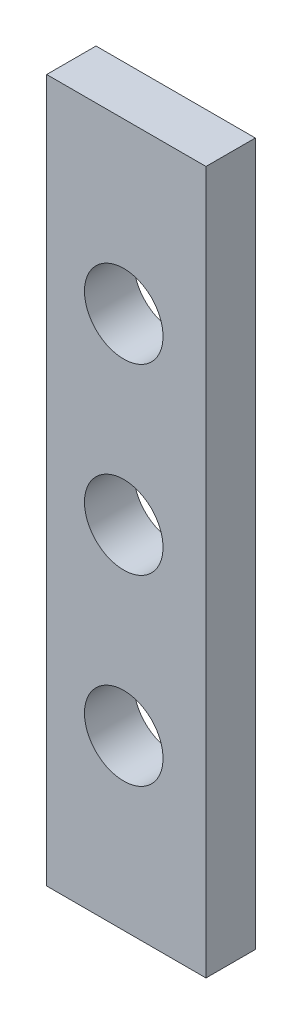
SolidWorks part; units mm, degrees
ref_plane "前视基准面" through (0, 0, 0) normal (0, 0, 1) x (1, 0, 0)
ref_plane "上视基准面" through (0, 0, 0) normal (0, 1, 0) x (1, 0, 0)
ref_plane "右视基准面" through (0, 0, 0) normal (1, 0, 0) x (0, 0, -1)
sketch "草图1" plane through (0, 0, 0) normal (0, 0, 1) x (1, 0, 0)
  line L6 (-130, -105) -> (-121.2816, -105)
  line L7 (-130, -105) -> (-130, -66.5374)
  line L8 (-130, -66.5374) -> (-121.2816, -66.5374)
  line L9 (-121.2816, -105) -> (-121.2816, -66.5374)
  point P1 (-121.2816, -66.5374)
extrude "凸台-拉伸1" add sketch "草图1" along normal blind 2.7
hole_wizard "打孔尺寸(%根据十字)槽沉头木螺钉的类型1" positions "草图2" profile "草图3" countersink size "M4" standard "GB"
sketch "草图2" plane through (40.4914, -131.0101, 7) normal (0, 0, 1) x (0, 1, 0)
  point P0 (35.2414, 166.273)
  point P3 (45.2414, 166.273)
  point P6 (55.2414, 166.273)
  point P9 (206.7788, 166.273)
  point P12 (216.7788, 166.273)
  point P15 (226.7788, 166.273)
sketch "草图3" plane through (-125.7816, -95.7687, 7) normal (1, 0, 0) x (0, -1, 0)
  line L0 (0, 0) -> (0, 20.2919)
  line L1 (0, 20.2919) -> (2.15, 19)
  line L2 (2.15, 19) -> (2.15, 1.85)
  line L3 (2.15, 1.85) -> (4, 0)
  line L4 (4, 0) -> (0, 0)
  line L5 (-2.15, 1.85) -> (-4, 0) construction
  line L6 (0, 20.2919) -> (-2.15, 19) construction
  line L7 (0, -6.35) -> (0, 107.95) construction
  dimension "孔直径" = 4.3
  dimension "孔深度" = 19
  dimension "近端锥形沉头孔直径" = 8
  dimension "近端锥形沉头孔角度" = 90
  dimension "导头角度" = 118
